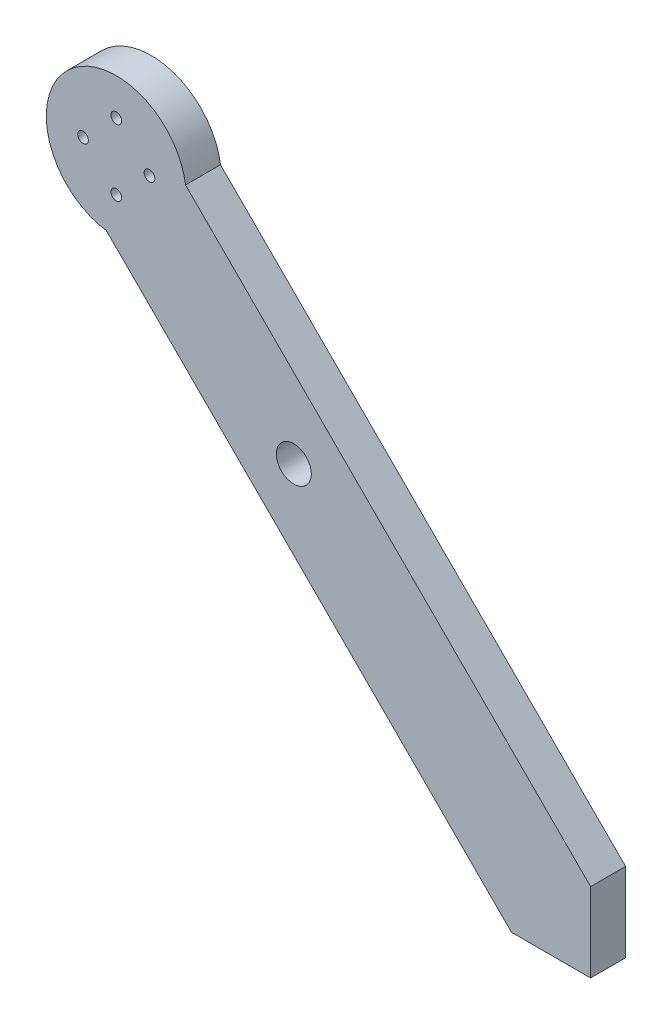
SolidWorks part; units mm, degrees
ref_plane "Plan de face" through (0, 0, 0) normal (0, 0, 1) x (1, 0, 0)
ref_plane "Plan de dessus" through (0, 0, 0) normal (0, 1, 0) x (1, 0, 0)
ref_plane "Plan de droite" through (0, 0, 0) normal (1, 0, 0) x (0, 0, -1)
sketch "Esquisse1" plane through (0, 0, 0) normal (0, 0, 1) x (1, 0, 0)
  line L0 (-22.6274, 0) -> (0, 0)
  line L1 (0, 0) -> (0, 22.6274)
  line L2 (32.3726, 55) -> (0, 22.6274) construction
  line L3 (0, 22.6274) -> (-32.3726, 55)
  line L4 (-32.3726, 55) -> (-124.2965, 146.9239)
  line L5 (-124.2965, 146.9239) -> (-146.9239, 124.2965)
  line L6 (-146.9239, 124.2965) -> (-55, 32.3726)
  line L7 (-55, 32.3726) -> (-22.6274, 0)
  line L8 (-32.3726, 55) -> (-55, 32.3726) construction
  circle A0 centre (-135.6102, 135.6102) radius 20
  dimension "D2" = 40
  dimension "D1" = 130
extrude "Boss.-Extru.1" add sketch "Esquisse1" along normal blind 10 contours A0 L6 L7 L0 L1 L3 L4 | L6 A0 L4 L5 | L4 A0 L6 L5 region at (-64.3798, 64.3798, 0) region at (-140.742, 140.742, 0) region at (-129.2859, 129.2859, 0)
sketch "Esquisse2" plane through (0, 0, 0) normal (0, 0, -1) x (-1, 0, 0)
  circle A3 centre (31.8198, 31.8198) radius 4.5
  circle A4 centre (14.1421, 14.1421) radius 4.5
  dimension "D1" = 9
  dimension "D2" = 9
extrude "Boss.-Extru.2" add sketch "Esquisse2" along normal up to surface (5 mm away)
sketch "Esquisse3" plane through (0, 0, 0) normal (0, 0, -1) x (-1, 0, 0)
  line L0 (135.6102, 135.6102) -> (149.7523, 149.7523) construction
  line L1 (135.6102, 135.6102) -> (135.6102, 145.1102) construction
  line L2 (135.6102, 135.6102) -> (135.6102, 145.1102) construction
  line L3 (135.6102, 135.6102) -> (145.1102, 135.6102) construction
  circle A0 centre (135.6102, 135.6102) radius 9.5 construction
  arc A1 (138.4386, 115.8112) -> (115.8112, 138.4386) centre (135.6102, 135.6102) ccw construction
  circle A2 centre (135.6102, 145.1102) radius 1.525
  circle A3 centre (145.1102, 135.6102) radius 1.525
  circle A4 centre (135.6102, 126.1102) radius 1.525
  circle A5 centre (126.1102, 135.6102) radius 1.525
  circle A6 centre (84.8528, 84.8528) radius 5
  dimension "D1" = 19
  dimension "D3" = 3.05
  dimension "D6" = 10
  dimension "D2" = 45
  dimension "D5" = 90
  dimension "D7" = 120
  dimension "D4" = 4
extrude "Enlèv. mat.-Extru.1" cut sketch "Esquisse3" against normal through all
